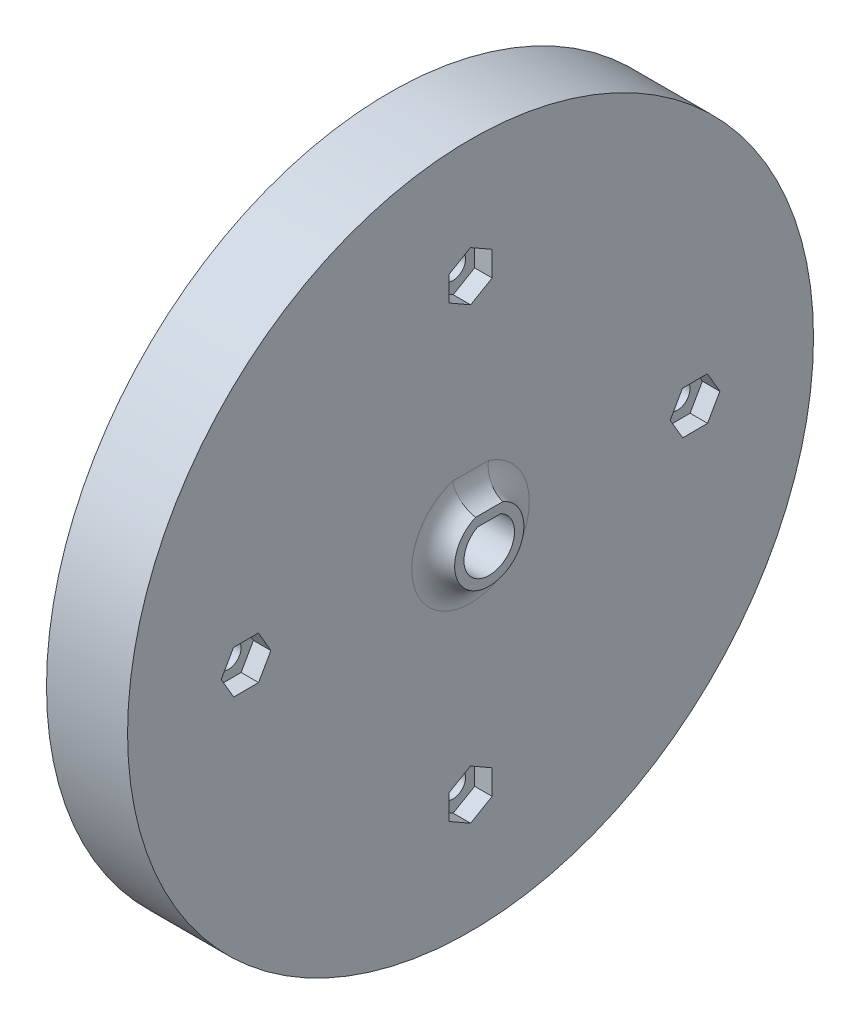
SolidWorks part; units mm, degrees
ref_plane "Front Plane" through (0, 0, 0) normal (0, 0, 1) x (1, 0, 0)
ref_plane "Top Plane" through (0, 0, 0) normal (0, 1, 0) x (1, 0, 0)
ref_plane "Right Plane" through (0, 0, 0) normal (1, 0, 0) x (0, 0, -1)
sketch "Sketch1" plane through (0, 0, 0) normal (1, 0, 0) x (0, 0, -1)
  circle A0 centre (0, 0) radius 55
  dimension "D1" = 110
extrude "Boss-Extrude1" add sketch "Sketch1" along normal blind 13
sketch "Sketch2" plane through (13, 0, 0) normal (1, 0, 0) x (0, 0, -1)
  line L0 (0, 0) -> (0, 3.6) construction
  line L1 (-1.8554, 3.6) -> (1.8554, 3.6)
  arc A0 (-1.8554, 3.6) -> (1.8554, 3.6) centre (0, 0) ccw
  point P7 (0, 3.6)
  dimension "D1" = 8.1
  dimension "D2" = 3.6
extrude "Cut-Extrude1" cut sketch "Sketch2" against normal up to surface (13 mm away) up to face at (0, 0, -55)
sketch "Sketch3" plane through (13, 0, 0) normal (1, 0, 0) x (0, 0, -1)
  line L0 (-1.8554, 3.6) -> (1.8554, 3.6)
  line L2 (-2.1892, 5.1) -> (2.1892, 5.1)
  arc A0 (-1.8554, 3.6) -> (1.8554, 3.6) centre (0, 0) ccw
  arc A1 (-2.1892, 5.1) -> (2.1892, 5.1) centre (0, 0) ccw
  point P6 (0, 3.6)
  dimension "D1" = 1.5
extrude "Boss-Extrude2" add sketch "Sketch3" along normal blind 3
fillet "Fillet1" radius 4 2 edges at (13, 5.1, 0) (13, -5.55, 0)
sketch "Sketch4" plane through (0, 0, 0) normal (-1, 0, 0) x (0, 0, 1)
  line L0 (0, 0) -> (0, 36) construction
  line L1 (0, 51.4) -> (0, 55) construction
  circle A0 centre (0, 36) radius 15.4
  circle A1 centre (0, 0) radius 55 construction
  circle A2 centre (36, 0) radius 15.4
  circle A3 centre (0, -36) radius 15.4
  circle A4 centre (-36, 0) radius 15.4
  point P18 (0, 0)
  dimension "D2" = 30.8
  dimension "D1" = 36
  dimension "D3" = 4
extrude "Cut-Extrude2" cut sketch "Sketch4" against normal blind 8.6
sketch "Sketch5" plane through (8.6, 0, 0) normal (-1, 0, 0) x (0, 0, 1)
  circle A0 centre (-36, 0) radius 2
  circle A1 centre (0, 36) radius 2
  circle A2 centre (36, 0) radius 2
  circle A3 centre (0, -36) radius 2
  circle A4 centre (-36, 0) radius 15.4 construction
  point P12 (0, 0)
  dimension "D1" = 4
  dimension "D3" = 36
  dimension "D2" = 4
extrude "Cut-Extrude3" cut sketch "Sketch5" against normal up to surface (4.4 mm away) up to face at (13, -0.225, 0)
sketch "Sketch8" plane through (13, 0, 0) normal (1, 0, 0) x (0, 0, -1)
  line L0 (-3.4404, 33.9916) -> (0.0191, 32.0163)
  line L1 (-33.9916, -3.4404) -> (-32.0163, 0.0191)
  line L2 (-32.0163, 0.0191) -> (-34.0247, 3.4595)
  line L3 (-34.0247, 3.4595) -> (-38.0084, 3.4404)
  line L4 (-38.0084, 3.4404) -> (-39.9837, -0.0191)
  line L5 (-39.9837, -0.0191) -> (-37.9753, -3.4595)
  line L6 (-37.9753, -3.4595) -> (-33.9916, -3.4404)
  line L7 (0.0191, 32.0163) -> (3.4595, 34.0247)
  line L8 (3.4595, 34.0247) -> (3.4404, 38.0084)
  line L9 (3.4404, 38.0084) -> (-0.0191, 39.9837)
  line L10 (-0.0191, 39.9837) -> (-3.4595, 37.9753)
  line L11 (-3.4595, 37.9753) -> (-3.4404, 33.9916)
  line L12 (33.9916, 3.4404) -> (32.0163, -0.0191)
  line L13 (32.0163, -0.0191) -> (34.0247, -3.4595)
  line L14 (34.0247, -3.4595) -> (38.0084, -3.4404)
  line L15 (38.0084, -3.4404) -> (39.9837, 0.0191)
  line L16 (39.9837, 0.0191) -> (37.9753, 3.4595)
  line L17 (37.9753, 3.4595) -> (33.9916, 3.4404)
  line L18 (3.4404, -33.9916) -> (-0.0191, -32.0163)
  line L19 (-0.0191, -32.0163) -> (-3.4595, -34.0247)
  line L20 (-3.4595, -34.0247) -> (-3.4404, -38.0084)
  line L21 (-3.4404, -38.0084) -> (0.0191, -39.9837)
  line L22 (0.0191, -39.9837) -> (3.4595, -37.9753)
  line L23 (3.4595, -37.9753) -> (3.4404, -33.9916)
  circle A0 centre (-36, 0) radius 3.45 construction
  circle A1 centre (36, 0) radius 2 construction
  circle A2 centre (0, 36) radius 3.45 construction
  circle A3 centre (36, 0) radius 3.45 construction
  circle A4 centre (0, -36) radius 3.45 construction
  point P39 (0, 0)
  dimension "D1" = 6.9
  dimension "D2" = 68.0163
  dimension "D3" = 4
extrude "Cut-Extrude4" cut sketch "Sketch8" against normal blind 2.8
fillet "Fillet2" radius 1.5 4 edges at (8.6, -36, 15.4) (8.6, 0, 51.4) (8.6, 0, -20.6) (8.6, 36, 15.4)
